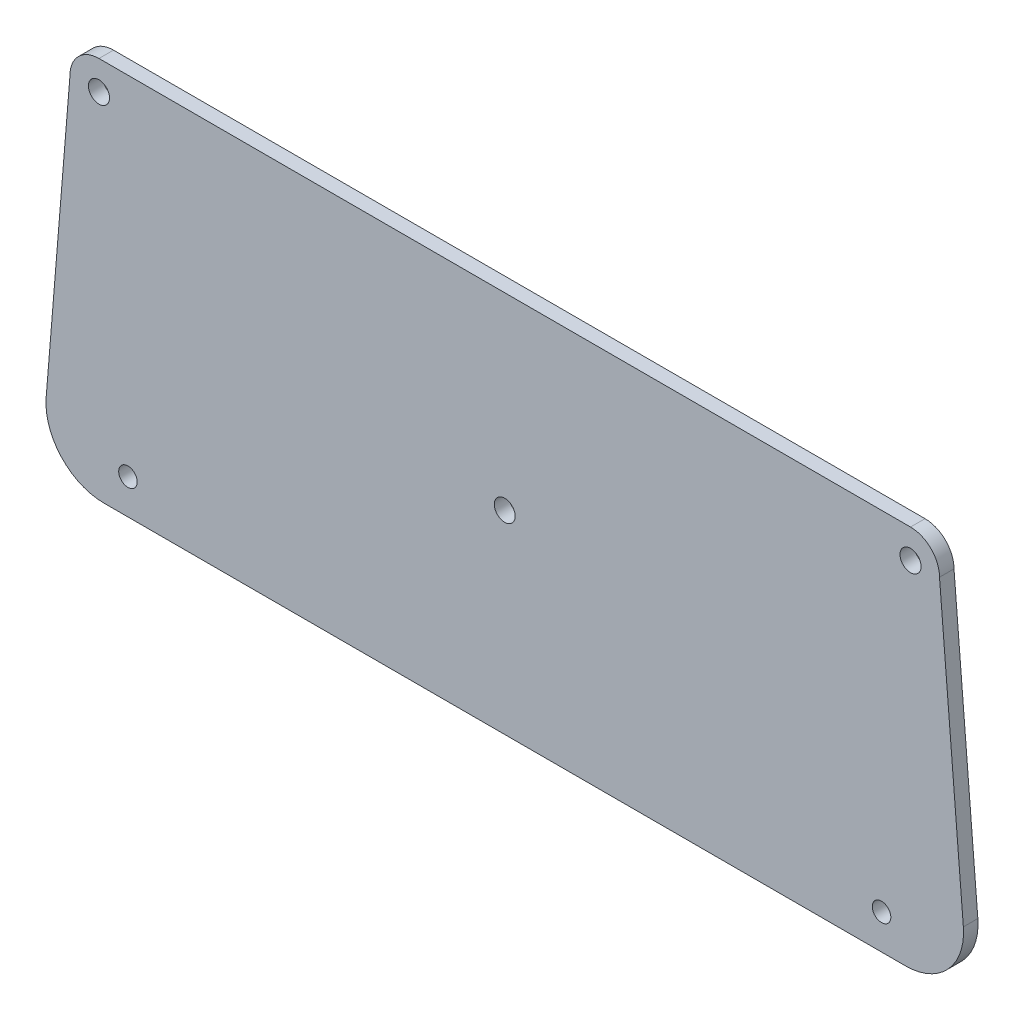
SolidWorks part; units mm, degrees
ref_plane "Front Plane" through (0, 0, 0) normal (0, 0, 1) x (1, 0, 0)
ref_plane "Top Plane" through (0, 0, 0) normal (0, 1, 0) x (1, 0, 0)
ref_plane "Right Plane" through (0, 0, 0) normal (1, 0, 0) x (0, 0, -1)
sketch "Sketch1" plane through (0, 0, 0) normal (0, 0, 1) x (1, 0, 0)
  line L0 (-87.2518, -38.0475) -> (115.9482, -38.0475)
  line L4 (-99.9518, -38.0475) -> (-37.476, -38.0475) construction
  line L5 (-87.2518, -38.0475) -> (-80.9018, 39.4225)
  line L6 (91.5724, -38.0475) -> (128.6482, -38.0475) construction
  line L7 (115.9482, 25.6983) -> (115.9482, -36.7775) construction
  line L8 (-72.2404, 37.6191) -> (-72.2404, 41.2259) construction
  line L9 (-76.8632, 41.2259) -> (-76.8632, 37.6191) construction
  line L10 (-72.7484, 41.7339) -> (-76.3552, 41.7339) construction
  line L11 (-76.3552, 37.1111) -> (-72.7484, 37.1111) construction
  line L12 (-72.2404, 37.6191) -> (-72.2404, 41.2259) construction
  line L13 (-76.8632, 41.2259) -> (-76.8632, 37.6191) construction
  line L14 (-72.7484, 41.7339) -> (-76.3552, 41.7339) construction
  line L15 (-76.3552, 37.1111) -> (-72.7484, 37.1111) construction
  line L16 (105.0516, 41.7339) -> (101.4448, 41.7339) construction
  line L17 (101.4448, 37.1111) -> (105.0516, 37.1111) construction
  line L18 (105.5596, 37.6191) -> (105.5596, 41.2259) construction
  line L19 (100.9368, 41.2259) -> (100.9368, 37.6191) construction
  line L20 (105.0516, 41.7339) -> (101.4448, 41.7339) construction
  line L21 (101.4448, 37.1111) -> (105.0516, 37.1111) construction
  line L22 (105.5596, 37.6191) -> (105.5596, 41.2259) construction
  line L23 (100.9368, 41.2259) -> (100.9368, 37.6191) construction
  line L24 (-74.5518, 45.7725) -> (103.2482, 45.7725)
  line L25 (109.5982, 39.4225) -> (115.9482, -38.0475)
  line L26 (-87.2518, -34.2894) -> (-87.2518, 24.2344) construction
  circle A0 centre (14.3482, 4.4975) radius 2.286
  circle A1 centre (-74.5518, 39.4225) radius 2.3114
  arc A2 (-74.5518, 45.7725) -> (-80.9018, 39.4225) centre (-74.5518, 39.4225) ccw
  circle A3 centre (103.2482, 39.4225) radius 2.3114
  arc A4 (109.5982, 39.4225) -> (103.2482, 45.7725) centre (103.2482, 39.4225) ccw
  circle A5 centre (96.8982, -30.4275) radius 2.032 construction
  circle A6 centre (96.8982, -30.4275) radius 2.032
  circle A7 centre (-68.2018, -30.4008) radius 2.032 construction
  circle A8 centre (-68.2018, -30.4008) radius 2.032
  point P24 (-74.5518, 39.4225)
  point P42 (-83.7191, -38.0475)
  point P45 (0, 0)
  dimension "D1" = 4.572
  dimension "D2" = 6.35
extrude "Boss-Extrude1" add sketch "Sketch1" along normal blind 3.175
fillet "Fillet1" radius 12.7 2 edges at (-87.2518, -38.0475, 1.5875) (115.9482, -38.0475, 1.5875)
